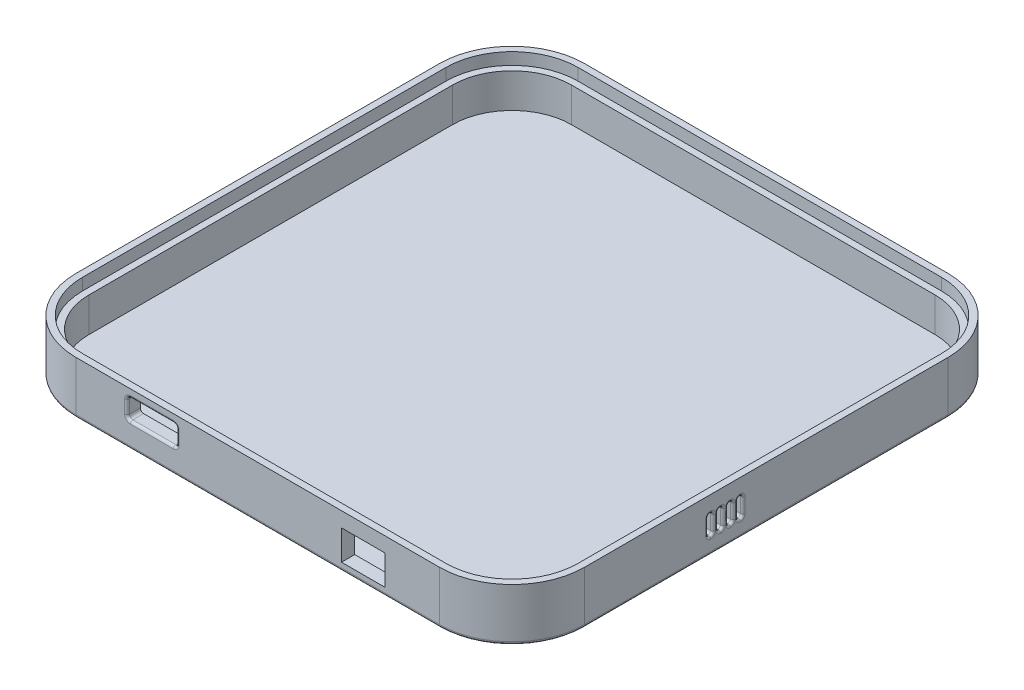
SolidWorks part; units mm, degrees
ref_plane "Front Plane" through (0, 0, 0) normal (0, 0, 1) x (1, 0, 0)
ref_plane "Top Plane" through (0, 0, 0) normal (0, 1, 0) x (1, 0, 0)
ref_plane "Right Plane" through (0, 0, 0) normal (1, 0, 0) x (0, 0, -1)
sketch "Sketch1" plane through (0, 0, 0) normal (0, 1, 0) x (1, 0, 0)
  line L0 (0, 75) -> (55, 75)
  line L1 (75, 55) -> (75, 0)
  line L2 (75, 0) -> (75, -55)
  line L3 (55, -75) -> (0, -75)
  line L4 (0, -75) -> (-55, -75)
  line L5 (-75, -55) -> (-75, 0)
  line L6 (-75, 0) -> (-75, 55)
  line L7 (-55, 75) -> (0, 75)
  line L8 (-55, 77) -> (0, 77)
  line L9 (0, 77) -> (55, 77)
  line L10 (77, 55) -> (77, 0)
  line L11 (77, 0) -> (77, -55)
  line L12 (55, -77) -> (0, -77)
  line L13 (0, -77) -> (-55, -77)
  line L14 (-77, -55) -> (-77, 0)
  line L15 (-77, 0) -> (-77, 55)
  arc A0 (55, 75) -> (75, 55) centre (55, 55) cw
  arc A1 (75, -55) -> (55, -75) centre (55, -55) cw
  arc A2 (-55, -75) -> (-75, -55) centre (-55, -55) cw
  arc A3 (-75, 55) -> (-55, 75) centre (-55, 55) cw
  arc A4 (55, 77) -> (77, 55) centre (55, 55) cw
  arc A5 (77, -55) -> (55, -77) centre (55, -55) cw
  arc A6 (-55, -77) -> (-77, -55) centre (-55, -55) cw
  arc A7 (-77, 55) -> (-55, 77) centre (-55, 55) cw
  point P24 (0, 0)
  dimension "D1" = 75
  dimension "D2" = 75
  dimension "D3" = 20
  dimension "D5" = 2
  dimension "D4" = 4
extrude "Boss-Extrude2" add sketch "Sketch1" along normal blind 14
sketch "Sketch4" plane through (0, 0, 0) normal (0, 1, 0) x (1, 0, 0)
  line L20 (55, 73) -> (-55, 73)
  line L21 (73, -55) -> (73, 55)
  line L22 (-55, -73) -> (55, -73)
  line L23 (-73, 55) -> (-73, -55)
  line L24 (55, 73) -> (-55, 73)
  line L25 (73, -55) -> (73, 55)
  line L26 (-55, -73) -> (55, -73)
  line L27 (-73, 55) -> (-73, -55)
  line L44 (55, 75) -> (-55, 75)
  line L45 (75, -55) -> (75, 55)
  line L46 (-55, -75) -> (55, -75)
  line L47 (-75, 55) -> (-75, -55)
  line L48 (55, 75) -> (-55, 75)
  line L49 (75, -55) -> (75, 55)
  line L50 (-55, -75) -> (55, -75)
  line L51 (-75, 55) -> (-75, -55)
  arc A24 (73, 55) -> (55, 73) centre (55, 55) ccw
  arc A25 (55, -73) -> (73, -55) centre (55, -55) ccw
  arc A26 (-73, -55) -> (-55, -73) centre (-55, -55) ccw
  arc A27 (-55, 73) -> (-73, 55) centre (-55, 55) ccw
  arc A28 (73, 55) -> (55, 73) centre (55, 55) ccw
  arc A29 (55, -73) -> (73, -55) centre (55, -55) ccw
  arc A30 (-73, -55) -> (-55, -73) centre (-55, -55) ccw
  arc A31 (-55, 73) -> (-73, 55) centre (-55, 55) ccw
  arc A52 (75, 55) -> (55, 75) centre (55, 55) ccw
  arc A53 (55, -75) -> (75, -55) centre (55, -55) ccw
  arc A54 (-75, -55) -> (-55, -75) centre (-55, -55) ccw
  arc A55 (-55, 75) -> (-75, 55) centre (-55, 55) ccw
  arc A56 (75, 55) -> (55, 75) centre (55, 55) ccw
  arc A57 (55, -75) -> (75, -55) centre (55, -55) ccw
  arc A58 (-75, -55) -> (-55, -75) centre (-55, -55) ccw
  arc A59 (-55, 75) -> (-75, 55) centre (-55, 55) ccw
  dimension "D1" = 2
  dimension "D2" = 0
extrude "Boss-Extrude3" add sketch "Sketch4" along normal blind 10.4
sketch "Sketch5" plane through (0, 0, 0) normal (0, -1, 0) x (1, 0, 0)
  line L8 (-55, -77) -> (55, -77)
  line L9 (77, -55) -> (77, 55)
  line L10 (55, 77) -> (-55, 77)
  line L11 (-77, 55) -> (-77, -55)
  line L12 (-55, -77) -> (55, -77)
  line L13 (77, -55) -> (77, 55)
  line L14 (55, 77) -> (-55, 77)
  line L15 (-77, 55) -> (-77, -55)
  arc A8 (-77, -55) -> (-55, -77) centre (-55, -55) ccw
  arc A9 (55, -77) -> (77, -55) centre (55, -55) ccw
  arc A10 (77, 55) -> (55, 77) centre (55, 55) ccw
  arc A11 (-55, 77) -> (-77, 55) centre (-55, 55) ccw
  arc A12 (-77, -55) -> (-55, -77) centre (-55, -55) ccw
  arc A13 (55, -77) -> (77, -55) centre (55, -55) ccw
  arc A14 (77, 55) -> (55, 77) centre (55, 55) ccw
  arc A15 (-55, 77) -> (-77, 55) centre (-55, 55) ccw
  dimension "D1" = 0
extrude "Boss-Extrude4" add sketch "Sketch5" along normal blind 2
sketch "Sketch6" plane through (0, 0, 77) normal (0, 0, 1) x (1, 0, 0)
  line L0 (-77, 14) -> (-77, -2) construction
  line L1 (-39.5, 5.5) -> (-24.5, 5.5)
  line L2 (-39.5, 5.5) -> (-39.5, 11.5)
  line L3 (-39.5, 11.5) -> (-24.5, 11.5)
  line L4 (-24.5, 5.5) -> (-24.5, 11.5)
  line L5 (-39.5, 5.5) -> (-24.5, 11.5) construction
  line L6 (-39.5, 11.5) -> (-24.5, 5.5) construction
  line L7 (55, -2) -> (-55, -2) construction
  line L12 (77, 14) -> (77, -2) construction
  line L13 (25.4, 9.5) -> (38.6, 9.5)
  line L14 (25.4, 9.5) -> (25.4, 0.5)
  line L15 (25.4, 0.5) -> (38.6, 0.5)
  line L16 (38.6, 9.5) -> (38.6, 0.5)
  point P0 (-32, 8.5)
  point P13 (25.4, 5)
  point P14 (38.6, 5)
  point P15 (32, 9.5)
  point P16 (32, 0.5)
  dimension "D1" = 15
  dimension "D2" = 45
  dimension "D3" = 10.5
  dimension "D4" = 6
  dimension "D5" = 13.2
  dimension "D6" = 9
  dimension "D7" = 45
  dimension "D8" = 7
extrude "Cut-Extrude1" cut sketch "Sketch6" against normal up to next
fillet "Fillet1" radius 1 4 edges at (-39.5, 5.5, 75) (-24.5, 5.5, 75) (-24.5, 11.5, 76) (-39.5, 11.5, 76)
sketch "Sketch7" plane through (77, 0, 0) normal (1, 0, 0) x (0, 0, -1)
  line L0 (-13.15, 8.9478) -> (-13.15, 3.0522)
  line L1 (-17.65, 8.9478) -> (-16.15, 8.9478)
  line L2 (-17.65, 8.9478) -> (-17.65, 3.0522)
  line L3 (-17.65, 3.0522) -> (-16.15, 3.0522)
  line L4 (-16.15, 8.9478) -> (-16.15, 3.0522)
  line L5 (-14.65, 8.9478) -> (-13.15, 8.9478)
  line L6 (-14.65, 8.9478) -> (-14.65, 3.0522)
  line L7 (-14.65, 3.0522) -> (-13.15, 3.0522)
  line L8 (-10.15, 8.9478) -> (-10.15, 3.0522)
  line L9 (-11.65, 8.9478) -> (-10.15, 8.9478)
  line L10 (-11.65, 8.9478) -> (-11.65, 3.0522)
  line L11 (-11.65, 3.0522) -> (-10.15, 3.0522)
  line L12 (-7.15, 8.9478) -> (-7.15, 3.0522)
  line L13 (-8.65, 8.9478) -> (-7.15, 8.9478)
  line L14 (-8.65, 8.9478) -> (-8.65, 3.0522)
  line L15 (-8.65, 3.0522) -> (-7.15, 3.0522)
  line L16 (-13.15, 6) -> (-11.65, 6) construction
  line L17 (-14.65, 6) -> (-16.15, 6) construction
  line L18 (-10.15, 6) -> (-8.65, 6) construction
  line L19 (-77, 14) -> (-77, -2) construction
  line L20 (-55, 14) -> (55, 14) construction
  point P22 (-12.4, 6)
  dimension "D1" = 1.5
  dimension "D3" = 64.6
  dimension "D4" = 8
  dimension "D2" = 4
extrude "Cut-Extrude2" cut sketch "Sketch7" against normal up to next
fillet "Fillet2" radius 0.75 32 edges at (73, 6, 7.15) (77, 6, 7.15) (73, 6, 10.15) (77, 6, 10.15) (73, 6, 13.15) (77, 6, 13.15) (73, 6, 16.15) (77, 6, 16.15) (75, 8.9478, 7.15) (73, 6, 8.65) (75, 3.0522, 8.65) (77, 6, 8.65) (75, 8.9478, 8.65) (75, 8.9478, 10.15) (73, 6, 11.65) (75, 3.0522, 11.65) (77, 6, 11.65) (75, 8.9478, 11.65) (75, 8.9478, 13.15) (73, 6, 14.65) (75, 3.0522, 14.65) (77, 6, 14.65) (75, 8.9478, 14.65) (73, 6, 17.65) (75, 3.0522, 17.65) (77, 6, 17.65) (75, 8.9478, 17.65) (75, 8.9478, 16.15) (75, 3.0522, 7.15) (75, 3.0522, 10.15) (75, 3.0522, 13.15) (75, 3.0522, 16.15)
fillet "Fillet3" radius 0.75 8 edges at (-24.7929, 11.2071, 77) (-24.5, 8.5, 77) (-24.7929, 5.7929, 77) (-32, 5.5, 77) (-39.2071, 5.7929, 77) (-39.5, 8.5, 77) (-39.2071, 11.2071, 77) (-32, 11.5, 77)
fillet "Fillet4" radius 1 8 edges at (70.5563, -2, 70.5563) (77, -2, 0) (70.5563, -2, -70.5563) (0, -2, -77) (-70.5563, -2, -70.5563) (-77, -2, 0) (-70.5563, -2, 70.5563) (0, -2, 77)
